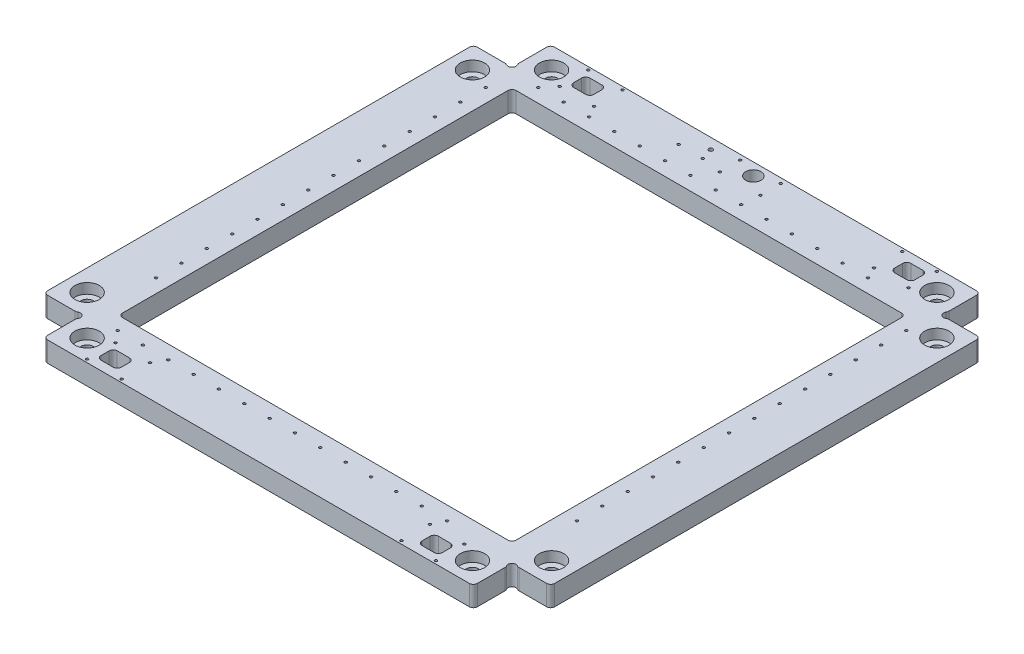
SolidWorks part; units mm, degrees
material "ASTM A36 Steel"
ref_plane "Front Plane" through (0, 0, 0) normal (0, 0, 1) x (1, 0, 0)
ref_plane "Top Plane" through (0, 0, 0) normal (0, 1, 0) x (1, 0, 0)
ref_plane "Right Plane" through (0, 0, 0) normal (1, 0, 0) x (0, 0, -1)
sketch "Sketch1" plane through (0, 0, 0) normal (0, 1, 0) x (1, 0, 0)
  line L1 (250, -250) -> (-250, -250)
  line L2 (250, -250) -> (250, 250)
  line L3 (250, 250) -> (-250, 250)
  line L4 (-250, -250) -> (-250, 250)
  line L5 (250, -250) -> (-250, 250) construction
  line L6 (250, 250) -> (-250, -250) construction
  point P0 (0, 0)
  dimension "D1" = 500
  dimension "D2" = 500
extrude "Boss-Extrude1" add sketch "Sketch1" along normal blind 20
sketch "Sketch2" plane through (0, 20, 0) normal (0, 1, 0) x (1, 0, 0)
  line L0 (250, 250) -> (-250, 250) construction
  line L10 (-250, 250) -> (-250, -250) construction
  line L15 (-250, 169) -> (-208, 169)
  line L16 (-250, 169) -> (-250, 211)
  line L17 (-174.5, 213.5) -> (-205.5, 213.5)
  line L27 (-250, 211) -> (-208, 211)
  line L33 (-208, 169) -> (-208, 211)
  line L35 (-250, 169) -> (-208, 211) construction
  line L36 (-250, 211) -> (-208, 169) construction
  line L37 (-169, 208) -> (-211, 208)
  line L38 (-169, 208) -> (-169, 250)
  line L39 (-169, 250) -> (-211, 250)
  line L40 (-211, 208) -> (-211, 250)
  line L41 (-169, 208) -> (-211, 250) construction
  line L42 (-169, 250) -> (-211, 208) construction
  line L43 (-208, 206) -> (-213, 211)
  line L44 (-174.5, 213.5) -> (-174.5, 244.5)
  line L45 (-174.5, 244.5) -> (-205.5, 244.5)
  line L46 (-205.5, 213.5) -> (-205.5, 244.5)
  line L47 (-174.5, 213.5) -> (-205.5, 244.5) construction
  line L48 (-174.5, 244.5) -> (-205.5, 213.5) construction
  line L49 (-213.5, 174.5) -> (-244.5, 174.5)
  line L50 (-213.5, 174.5) -> (-213.5, 205.5)
  line L51 (-213.5, 205.5) -> (-244.5, 205.5)
  line L52 (-244.5, 174.5) -> (-244.5, 205.5)
  line L53 (-213.5, 174.5) -> (-244.5, 205.5) construction
  line L54 (-213.5, 205.5) -> (-244.5, 174.5) construction
  line L55 (-206, 208) -> (-211, 213)
  line L56 (-213, 211) -> (-211, 213) construction
  point P1 (-229, 190)
  point P5 (-190, 229)
  point P23 (-229, 190)
  point P27 (-190, 229)
  dimension "D1" = 5
  dimension "D2" = 45
  dimension "D3" = 42
  dimension "D4" = 31
  dimension "D5" = 45
  dimension "D6" = 5
  dimension "D7" = 60
hole_wizard "Bearing Press Fit" positions "Sketch8" profile "Sketch9" hole size "Ø12.0" standard "ANSI Metric" end condition through all
sketch "Sketch8" plane through (0, 20, 0) normal (0, 1, 0) x (1, 0, 0)
  line L1 (-169, 250) -> (-211, 208) construction
  point P8 (-190, 229)
  point P12 (-229, 190)
sketch "Sketch9" plane through (-190, 20, -229) normal (1, 0, 0) x (0, 0, 1)
  line L0 (0, 0) -> (0, 20)
  line L1 (0, 20) -> (6, 20)
  line L2 (6, 20) -> (6, 0)
  line L5 (6, 0) -> (0, 0)
  line L11 (0, -6.35) -> (0, 107.95) construction
  dimension "Thru Hole Dia." = 12
  dimension "Thru Hole Depth" = 20
ref_axis "Axis1" through (0, 21, 0) along (0, -1, 0)
pattern_circular "CirPattern1" count 4 over 360 about axis through (0, 21, 0) along (0, -1, 0) of "Bearing Press Fit"
sketch "Sketch5" plane through (0, 20, 0) normal (0, 1, 0) x (1, 0, 0)
  line L1 (194, -194) -> (-194, -194)
  line L2 (194, -194) -> (194, 194)
  line L3 (194, 194) -> (-194, 194)
  line L4 (-194, -194) -> (-194, 194)
  line L5 (194, -194) -> (-194, 194) construction
  line L6 (194, 194) -> (-194, -194) construction
  point P0 (0, 0)
  dimension "D1" = 388
extrude "Cut-Extrude1" cut sketch "Sketch5" against normal up to surface (20 mm away) up to face at (-229, 0, 196)
sketch "Sketch10" plane through (0, 0, 0) normal (0, 1, 0) x (1, 0, 0)
  line L5 (194, 194) -> (-194, 194) construction
  line L6 (214, -214) -> (-214, -214)
  line L14 (214, -214) -> (214, 214)
  line L15 (214, 214) -> (-214, 214)
  line L16 (-214, -214) -> (-214, 214)
  line L17 (214, -214) -> (-214, 214) construction
  line L18 (214, 214) -> (-214, -214) construction
  line L19 (201.5, -201.5) -> (-201.5, -201.5)
  line L20 (201.5, -201.5) -> (201.5, 201.5)
  line L21 (201.5, 201.5) -> (-201.5, 201.5)
  line L22 (-201.5, -201.5) -> (-201.5, 201.5)
  line L23 (201.5, -201.5) -> (-201.5, 201.5) construction
  line L24 (201.5, 201.5) -> (-201.5, -201.5) construction
  point P0 (0, 0)
  point P6 (0, 0)
  dimension "D2" = 7.5
  dimension "D1" = 12.5
extrude "Linear Rail Slot" cut sketch "Sketch10" along normal blind 2.5
fillet "Fillet2" radius 4 4 edges at (-194, 10, 194) (194, 10, 194) (194, 10, -194) (-194, 10, -194)
sketch "Sketch11" plane through (0, 2.5, 0) normal (0, -1, 0) x (1, 0, 0)
  line L0 (-204, 207.5) -> (156, 207.5)
  line L1 (-201.5, 201.5) -> (201.5, 201.5) construction
  line L3 (-214, -214) -> (-214, 214) construction
  point P16 (143.5, 207.5)
  point P18 (118.5, 207.5)
  point P19 (93.5, 207.5)
  point P20 (68.5, 207.5)
  point P21 (43.5, 207.5)
  point P22 (18.5, 207.5)
  point P23 (-6.5, 207.5)
  point P24 (-31.5, 207.5)
  point P25 (-56.5, 207.5)
  point P26 (-81.5, 207.5)
  point P28 (-106.5, 207.5)
  point P29 (-131.5, 207.5)
  point P30 (-156.5, 207.5)
  point P31 (-181.5, 207.5)
  dimension "D1" = 360
  dimension "D2" = 6
  dimension "D4" = 14
  dimension "D5" = 25
  dimension "D6" = 10
  dimension "D3" = 12.5
hole_wizard "Tap Drill for M3x0.5 Tap1" positions "Sketch12" profile "Sketch13" hole size "M3x0.5" standard "ANSI Metric" end condition through all
sketch "Sketch12" plane through (0, 2.5, 0) normal (0, -1, 0) x (-1, 0, 0)
  line L0 (204, -207.5) -> (-156, -207.5) construction
  point P28 (-143.5, -207.5)
  point P31 (-118.5, -207.5)
  point P34 (-93.5, -207.5)
  point P37 (-68.5, -207.5)
  point P40 (-43.5, -207.5)
  point P43 (-18.5, -207.5)
  point P46 (6.5, -207.5)
  point P49 (31.5, -207.5)
  point P51 (56.5, -207.5)
  point P54 (81.5, -207.5)
  point P57 (106.5, -207.5)
  point P61 (131.5, -207.5)
  point P64 (156.5, -207.5)
  point P67 (181.5, -207.5)
sketch "Sketch13" plane through (143.5, 2.5, 207.5) normal (1, 0, 0) x (0, 0, -1)
  line L0 (0, 0) -> (0, 17.5)
  line L1 (0, 17.5) -> (1.25, 17.5)
  line L2 (1.25, 17.5) -> (1.25, 0)
  line L5 (1.25, 0) -> (0, 0)
  line L11 (0, -6.35) -> (0, 107.95) construction
  dimension "Thru Hole Dia." = 2.5
  dimension "Thru Hole Depth" = 17.5
sketch "Sketch14" plane through (0, 0, 0) normal (0, -1, 0) x (1, 0, 0)
  line L1 (-156.5, 213.5) -> (-181.5, 213.5)
  line L2 (-152.5, 217.5) -> (-152.5, 219.5)
  line L3 (-156.5, 223.5) -> (-181.5, 223.5)
  line L4 (-185.5, 217.5) -> (-185.5, 219.5)
  line L5 (-152.5, 213.5) -> (-185.5, 223.5) construction
  line L6 (-152.5, 223.5) -> (-185.5, 213.5) construction
  line L7 (-201.5, 201.5) -> (201.5, 201.5) construction
  line L8 (-181.5, 207.5) -> (-156.5, 207.5) construction
  line L19 (-6.5, 213.5) -> (-31.5, 213.5)
  line L25 (-2.5, 217.5) -> (-2.5, 219.5)
  line L26 (-6.5, 223.5) -> (-31.5, 223.5)
  line L31 (-35.5, 217.5) -> (-35.5, 219.5)
  line L32 (-2.5, 213.5) -> (-35.5, 223.5) construction
  line L33 (-2.5, 223.5) -> (-35.5, 213.5) construction
  line L34 (-31.5, 207.5) -> (-6.5, 207.5) construction
  line L35 (143.5, 213.5) -> (118.5, 213.5)
  line L36 (147.5, 217.5) -> (147.5, 219.5)
  line L37 (143.5, 223.5) -> (118.5, 223.5)
  line L38 (114.5, 217.5) -> (114.5, 219.5)
  line L39 (147.5, 213.5) -> (114.5, 223.5) construction
  line L40 (147.5, 223.5) -> (114.5, 213.5) construction
  line L41 (118.5, 207.5) -> (143.5, 207.5) construction
  arc A3 (-152.5, 219.5) -> (-156.5, 223.5) centre (-156.5, 219.5) ccw
  arc A4 (-156.5, 213.5) -> (-152.5, 217.5) centre (-156.5, 217.5) ccw
  arc A5 (-181.5, 213.5) -> (-185.5, 217.5) centre (-181.5, 217.5) cw
  arc A6 (-181.5, 223.5) -> (-185.5, 219.5) centre (-181.5, 219.5) ccw
  arc A7 (-2.5, 219.5) -> (-6.5, 223.5) centre (-6.5, 219.5) ccw
  arc A8 (-6.5, 213.5) -> (-2.5, 217.5) centre (-6.5, 217.5) ccw
  arc A9 (-31.5, 213.5) -> (-35.5, 217.5) centre (-31.5, 217.5) cw
  arc A10 (-31.5, 223.5) -> (-35.5, 219.5) centre (-31.5, 219.5) ccw
  arc A11 (147.5, 219.5) -> (143.5, 223.5) centre (143.5, 219.5) ccw
  arc A12 (143.5, 213.5) -> (147.5, 217.5) centre (143.5, 217.5) ccw
  arc A13 (118.5, 213.5) -> (114.5, 217.5) centre (118.5, 217.5) cw
  arc A14 (118.5, 223.5) -> (114.5, 219.5) centre (118.5, 219.5) ccw
  point P0 (-169, 218.5)
  point P12 (-169, 207.5)
  point P26 (-19, 218.5)
  point P45 (131, 218.5)
  dimension "D5" = 3
  dimension "D4" = 4
  dimension "D1" = 33
  dimension "D2" = 12
  dimension "D3" = 10
  dimension "D7" = 25
  dimension "D6" = 150
mirror "Mirror5" about plane through (0, 0, 0) normal (0, 0, 1) of "Tap Drill for M3x0.5 Tap1"
ref_plane "Plane1" through (0, 0, 0) normal (-0.7071, 0, 0.7071) x (0.7071, 0, 0.7071)
mirror "Mirror6" about plane through (0, 0, 0) normal (-0.7071, 0, 0.7071) of "Mirror5"
sketch "Sketch19" plane through (0, 2.5, 0) normal (0, -1, 0) x (1, 0, 0)
  line L0 (-198.5, 201.5) -> (-198.5, 214)
  line L1 (-201.5, 201.5) -> (201.5, 201.5) construction
  line L2 (-214, 214) -> (214, 214) construction
  line L3 (-198.5, 214) -> (-214, 214)
  line L4 (-214, 214) -> (-214, 198.5)
  line L5 (-214, -214) -> (-214, 214) construction
  line L6 (-214, 198.5) -> (-201.5, 198.5)
  line L7 (-201.5, -201.5) -> (-201.5, 201.5) construction
  line L8 (-201.5, 198.5) -> (-201.5, 201.5)
  line L9 (-201.5, 201.5) -> (-198.5, 201.5)
  dimension "D1" = 3
extrude "Boss-Extrude2" add sketch "Sketch19" along normal up to surface (2.5 mm away) up to face at (-229, 0, 196)
pattern_circular "CirPattern4" count 4 over 360 about axis through (0, 21, 0) along (0, -1, 0) of "Boss-Extrude2"
sketch "Sketch20" plane through (0, 20, 0) normal (0, 1, 0) x (1, 0, 0)
  line L5 (-250, -250) -> (250, -250) construction
  line L20 (148.3, -225) -> (168.3, -241) construction
  line L23 (168.3, -225) -> (148.3, -241) construction
  line L28 (122, -247) -> (172, -219) construction
  line L29 (172, -247) -> (122, -219) construction
  line L30 (172, -219) -> (122, -219) construction
  line L31 (122, -247) -> (122, -219) construction
  line L32 (172, -247) -> (122, -247) construction
  line L33 (172, -247) -> (172, -219) construction
  line L34 (164.3, -241) -> (152.3, -241)
  line L35 (148.3, -229) -> (148.3, -237)
  line L36 (164.3, -225) -> (152.3, -225)
  line L37 (168.3, -229) -> (168.3, -237)
  arc A12 (152.3, -225) -> (148.3, -229) centre (152.3, -229) ccw
  arc A13 (148.3, -237) -> (152.3, -241) centre (152.3, -237) ccw
  arc A14 (168.3, -237) -> (164.3, -241) centre (164.3, -237) cw
  arc A15 (168.3, -229) -> (164.3, -225) centre (164.3, -229) ccw
  circle A16 centre (190, -229) radius 6 construction
  point P65 (158.3, -233)
  point P66 (147, -233)
  point P67 (158.3, -233)
  dimension "D7" = 31.7
  dimension "D8" = 11.3
  dimension "D6" = 4
  dimension "D1" = 28
  dimension "D2" = 50
  dimension "D3" = 17
  dimension "D4" = 20
  dimension "D5" = 16
extrude "Cut-Extrude3" cut sketch "Sketch20" against normal through all
hole_wizard "Tap Drill for M3x0.5 Tap6" positions "Sketch39" profile "Sketch40" hole size "M3x0.5" standard "ANSI Metric"
sketch "Sketch39" plane through (0, 20, 0) normal (0, 1, 0) x (1, 0, 0)
  line L1 (172, -247) -> (138, -247)
  line L2 (172, -247) -> (172, -219)
  line L3 (172, -219) -> (138, -219)
  line L4 (138, -247) -> (138, -219)
  line L5 (-250, -250) -> (250, -250) construction
  circle A0 centre (190, -229) radius 6 construction
  point P1 (172, -247)
  point P2 (138, -219)
  point P99 (172, -219)
  point P100 (138, -247)
  dimension "D1" = 34
  dimension "D2" = 28
  dimension "D3" = 3
  dimension "D4" = 18
sketch "Sketch40" plane through (172, 20, 247) normal (1, 0, 0) x (0, 0, 1)
  line L0 (0, 0) -> (0, 20)
  line L1 (0, 20) -> (1.25, 20)
  line L2 (1.25, 20) -> (1.25, 0)
  line L5 (1.25, 0) -> (0, 0)
  line L10 (0, 20) -> (-1.25, 20) construction
  line L11 (0, -6.35) -> (0, 107.95) construction
  dimension "Hole Dia." = 2.5
  dimension "Hole Depth" = 20
  dimension "Drill Angle" = 180
mirror "Mirror8" about plane through (0, 0, 0) normal (1, 0, 0) of "Tap Drill for M3x0.5 Tap6", "Cut-Extrude3"
mirror "Mirror9" about plane through (0, 0, 0) normal (0, 0, 1) of "Mirror8"
sketch "Sketch27" plane through (0, 20, 0) normal (0, 1, 0) x (1, 0, 0)
  line L1 (250, -250) -> (211.9, -250)
  line L2 (250, -250) -> (250, -211.9)
  line L3 (250, -211.9) -> (211.9, -211.9)
  line L4 (211.9, -250) -> (211.9, -211.9)
  dimension "D1" = 38.1
extrude "Cut-Extrude4" cut sketch "Sketch27" against normal up to surface (20 mm away) up to face at (172, 0, -245.75)
sketch "Sketch47" plane through (0, 0, 0) normal (0, -1, 0) x (1, 0, 0)
  line L0 (211.9, 211.9) -> (214.7284, 214.7284) construction
  line L1 (211.9, 211.9) -> (250, 211.9) construction
  circle A0 centre (214.7284, 214.7284) radius 4
  dimension "D1" = 8
  dimension "D2" = 45
extrude "Cut-Extrude5" cut sketch "Sketch47" against normal up to surface (20 mm away) up to face at (70.6333, 20, 70.6333)
pattern_circular "CirPattern3" count 4 over 360 about axis through (0, 21, 0) along (0, -1, 0) of "Cut-Extrude4", "Cut-Extrude5"
fillet "Fillet5" radius 4 16 edges at (198.5, 1.25, 214) (198.5, 1.25, 201.5) (201.5, 1.25, 198.5) (214, 1.25, 198.5) (-214, 1.25, 198.5) (-198.5, 1.25, 214) (-201.5, 1.25, 198.5) (-198.5, 1.25, 201.5) (-214, 1.25, -198.5) (-198.5, 1.25, -214) (-198.5, 1.25, -201.5) (-201.5, 1.25, -198.5) (198.5, 1.25, -201.5) (198.5, 1.25, -214) (201.5, 1.25, -198.5) (214, 1.25, -198.5)
hole_wizard "Tap Drill for M3x0.5 Tap4" positions "Sketch35" profile "Sketch36" hole size "M3x0.5" standard "ANSI Metric" end condition up to next
sketch "Sketch35" plane through (0, 20, 0) normal (0, 1, 0) x (1, 0, 0)
  line L1 (20, 225) -> (-20, 225)
  line L2 (20, 225) -> (20, 245)
  line L3 (20, 245) -> (-20, 245)
  line L4 (-20, 225) -> (-20, 245)
  line L5 (20, 225) -> (-20, 245) construction
  line L6 (20, 245) -> (-20, 225) construction
  line L7 (211.9, 250) -> (-211.9, 250) construction
  point P2 (-20, 245)
  point P53 (20, 225)
  point P54 (20, 245)
  point P55 (-20, 225)
  point P69 (0, 235)
  dimension "D1" = 20
  dimension "D2" = 40
  dimension "D3" = 15
sketch "Sketch36" plane through (-20, 20, -245) normal (1, 0, 0) x (0, 0, 1)
  line L0 (0, 0) -> (0, 20)
  line L1 (0, 20) -> (1.25, 20)
  line L2 (1.25, 20) -> (1.25, 0)
  line L5 (1.25, 0) -> (0, 0)
  line L11 (0, -6.35) -> (0, 107.95) construction
  dimension "Thru Hole Dia." = 2.5
  dimension "Thru Hole Depth" = 20
hole_wizard "Ø15.0 (15) Diameter Hole2" positions "Sketch37" profile "Sketch38" hole size "Ø15.0" standard "ANSI Metric" end condition up to next
sketch "Sketch37" plane through (0, 20, 0) normal (0, 1, 0) x (1, 0, 0)
  circle A0 centre (0, 235) radius 1.25 construction
  point P0 (0, 238)
  dimension "D1" = 3
sketch "Sketch38" plane through (0, 20, -238) normal (1, 0, 0) x (0, 0, 1)
  line L0 (0, 0) -> (0, 20)
  line L1 (0, 20) -> (7.5, 20)
  line L2 (7.5, 20) -> (7.5, 0)
  line L5 (7.5, 0) -> (0, 0)
  line L11 (0, -6.35) -> (0, 107.95) construction
  dimension "Thru Hole Dia." = 15
  dimension "Thru Hole Depth" = 20
chamfer "Chamfer1" [suppressed] distance 2 angle 45
hole_wizard "Ø24.0 (24) Diameter Hole1" positions "Sketch41" profile "Sketch42" hole size "Ø24.0" standard "ANSI Metric"
sketch "Sketch41" plane through (0, 20, 0) normal (0, 1, 0) x (1, 0, 0)
  point P0 (-229, -190)
  point P3 (-190, -229)
  point P6 (190, -229)
  point P9 (229, -190)
  point P12 (229, 190)
  point P15 (190, 229)
  point P18 (-190, 229)
  point P21 (-229, 190)
sketch "Sketch42" plane through (-229, 20, 190) normal (1, 0, 0) x (0, 0, 1)
  line L0 (0, 0) -> (0, 10)
  line L1 (0, 10) -> (12, 10)
  line L2 (12, 10) -> (12, 0)
  line L5 (12, 0) -> (0, 0)
  line L10 (0, 10) -> (-12, 10) construction
  line L11 (0, -6.35) -> (0, 107.95) construction
  dimension "Hole Dia." = 24
  dimension "Hole Depth" = 10
  dimension "Drill Angle" = 180
chamfer "Chamfer2" [suppressed] distance 1 angle 45
fillet "Fillet6" radius 4 16 edges at (250, 10, -211.9) (211.9, 10, -250) (-211.9, 10, -250) (-250, 10, -211.9) (211.9, 10, 250) (250, 10, 211.9) (-211.9, 10, 250) (-250, 10, 211.9) (-217.5569, 10, 211.9) (-217.5569, 10, -211.9) (-211.9, 10, -217.5569) (211.9, 10, -217.5569) (217.5569, 10, -211.9) (211.9, 10, 217.5569) (-211.9, 10, 217.5569) (217.5569, 10, 211.9)
hole_wizard "Tap Drill for M3x0.5 Tap7" positions "Sketch43" profile "Sketch44" hole size "M3x0.5" standard "ANSI Metric" end condition up to next
sketch "Sketch43" plane through (0, 20, 0) normal (0, 1, 0) x (1, 0, 0)
  line L0 (-63.7737, 228) -> (-39.7737, 228) construction
  line L2 (207.9, 250) -> (-207.9, 250) construction
  circle A0 centre (-20, 225) radius 1.25 construction
  point P1 (-63.7737, 228)
  point P2 (-39.7737, 228)
  dimension "D3" = 20
  dimension "D1" = 22
  dimension "D2" = 24
sketch "Sketch44" plane through (-63.7737, 20, -228) normal (1, 0, 0) x (0, 0, 1)
  line L0 (0, 0) -> (0, 20)
  line L1 (0, 20) -> (1.25, 20)
  line L2 (1.25, 20) -> (1.25, 0)
  line L5 (1.25, 0) -> (0, 0)
  line L11 (0, -6.35) -> (0, 107.95) construction
  dimension "Thru Hole Dia." = 2.5
  dimension "Thru Hole Depth" = 20
hole_wizard "Ø4.0 (4) Diameter Hole1" positions "Sketch45" profile "Sketch46" hole size "Ø4.0" standard "ANSI Metric" end condition up to next
sketch "Sketch45" plane through (0, 20, 0) normal (0, 1, 0) x (1, 0, 0)
  circle A0 centre (-63.7737, 228) radius 1.25 construction
  point P0 (-43.4737, 239.5)
  dimension "D1" = 20.3
  dimension "D2" = 11.5
sketch "Sketch46" plane through (-43.4737, 20, -239.5) normal (1, 0, 0) x (0, 0, 1)
  line L0 (0, 0) -> (0, 20)
  line L1 (0, 20) -> (2, 20)
  line L2 (2, 20) -> (2, 0)
  line L5 (2, 0) -> (0, 0)
  line L11 (0, -6.35) -> (0, 107.95) construction
  dimension "Thru Hole Dia." = 4
  dimension "Thru Hole Depth" = 20
